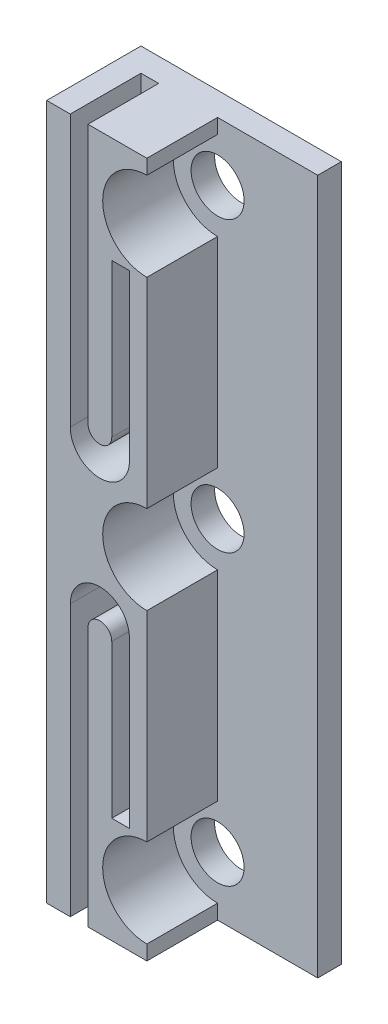
SolidWorks part; units mm, degrees
ref_plane "Plan de face" through (0, 0, 0) normal (0, 0, 1) x (1, 0, 0)
ref_plane "Plan de dessus" through (0, 0, 0) normal (0, 1, 0) x (1, 0, 0)
ref_plane "Plan de droite" through (0, 0, 0) normal (1, 0, 0) x (0, 0, -1)
sketch "Esquisse1" plane through (0, 0, 0) normal (0, 0, 1) x (1, 0, 0)
  line L1 (0, 0) -> (17, 0)
  line L2 (0, 0) -> (0, -59)
  line L3 (0, -59) -> (17, -59)
  line L4 (17, 0) -> (17, -59)
  dimension "D1" = 17
  dimension "D2" = 59
extrude "Boss.-Extru.1" add sketch "Esquisse1" along normal blind 2
sketch "Esquisse2" plane through (0, 0, 2) normal (0, 0, 1) x (1, 0, 0)
  line L0 (0, -59) -> (17, -59) construction
  line L1 (0, 0) -> (8.5, 0)
  line L2 (0, 0) -> (0, -59)
  line L3 (0, -59) -> (8.5, -59)
  line L4 (8.5, 0) -> (8.5, -59)
extrude "Boss.-Extru.2" add sketch "Esquisse2" along normal blind 6
sketch "Esquisse3" plane through (0, 0, 8) normal (0, 0, 1) x (1, 0, 0)
  line L0 (0, -59) -> (8.5, -59) construction
  line L1 (2, -59) -> (3.5, -59)
  line L2 (2, -59) -> (2, 0)
  line L3 (2, 0) -> (3.5, 0)
  line L4 (3.5, -59) -> (3.5, 0)
  line L5 (8.5, 0) -> (0, 0) construction
  line L6 (8.5, -59) -> (8.5, 0) construction
  line L7 (2, -23) -> (3.5, -23)
  line L8 (5.5199, -50) -> (7.0199, -50)
  line L9 (5.5199, -50) -> (5.5199, -9)
  line L10 (5.5199, -9) -> (7.0199, -9)
  line L11 (7.0199, -50) -> (7.0199, -9)
  line L12 (3.5, -37) -> (5.5199, -37)
  line L13 (3.5, -23) -> (5.5199, -23)
  line L14 (5.5199, -23) -> (7.0908, -23)
  line L15 (2, -36) -> (3.5, -36)
  line L16 (3.5, -36) -> (5.5199, -36)
  line L17 (5.5199, -36) -> (7.0199, -36)
  line L18 (3.5, -22) -> (5.5199, -22)
  arc A0 (2, -23) -> (7.0199, -23) centre (4.51, -23) ccw
  arc A1 (3.5, -37) -> (5.5199, -37) centre (4.51, -37) cw
  arc A3 (2, -36) -> (7.0199, -36) centre (4.51, -36) cw
  arc A4 (3.5, -22) -> (5.5199, -22) centre (4.51, -22) ccw
  point P14 (6.2699, -9)
  line M10 (0, -59) -> (8.5, -59)
  line M12 (8.5, 0) -> (0, 0)
  dimension "D1" = 1.5
  dimension "D2" = 5
  dimension "D3" = 1.5
  dimension "D4" = 9
  dimension "D5" = 9
  dimension "D6" = 13
  dimension "D7" = 14
  dimension "D8" = 14
  dimension "D9" = 1
  dimension "D10" = 1
extrude "Enlèv. mat.-Extru.1" cut sketch "Esquisse3" against normal blind 6 contours L9 L14 L11 L10 | L7 A0 L4 | L9 A0 L14 | L17 L9 L8 L11 | L15 L2 L4 M10 | A3 L4 L16 A1 L9 | A3 L15 L4 | A3 L9 L17 | A4 L13 L4 A0 L9 | L2 L7 L4 M12 | A4 L4 L13 | A4 L13 L9 | L4 A1 L16 | L16 A1 L9 region at (2.75, -47.5, 8) region at (2.8814, -35.0894, 8) region at (3.7155, -36.2252, 8) region at (2.75, -11.5, 8) region at (2.8814, -23.9106, 8) region at (4.51, -34.7785, 8) region at (6.2699, -43, 8) region at (5.3045, -36.2252, 8) region at (4.51, -24.2215, 8) region at (3.7155, -22.7748, 8) region at (6.1386, -35.0894, 8) region at (6.1386, -23.9106, 8) region at (6.2699, -16, 8) region at (5.3045, -22.7748, 8)
sketch "Esquisse4" plane through (0, 0, 8) normal (0, 0, 1) x (1, 0, 0)
  line L2 (3.5, -59) -> (8.5, -59) construction
  line L3 (17, -59) -> (17, 0) construction
  line L4 (0, 0) -> (0, -59) construction
  line L5 (8.5, -59) -> (8.5, 0) construction
  line L6 (8.5, 0) -> (3.5, 0) construction
  circle A0 centre (8.5, -29.5) radius 2.25
  circle A1 centre (8.5, -54) radius 2.25
  circle A2 centre (8.5, -5) radius 2.25
  point P8 (6, -59)
  dimension "D1" = 4.5
  dimension "D2" = 4.5
  dimension "D3" = 4.5
  dimension "D4" = 29.5
  dimension "D5" = 17
  dimension "D6" = 5
  dimension "D7" = 8.5
  dimension "D8" = 5
extrude "Enlèv. mat.-Extru.4" cut sketch "Esquisse4" against normal blind 22
sketch "Esquisse6" plane through (0, 0, 8) normal (0, 0, 1) x (1, 0, 0)
  circle A0 centre (8.5, -29.5) radius 3.75
  circle A1 centre (8.5, -5) radius 3.75
  circle A2 centre (8.5, -54) radius 3.75
  dimension "D1" = 7.5
  dimension "D2" = 7.5
  dimension "D3" = 7.5
extrude "Enlèv. mat.-Extru.5" cut sketch "Esquisse6" against normal blind 6
